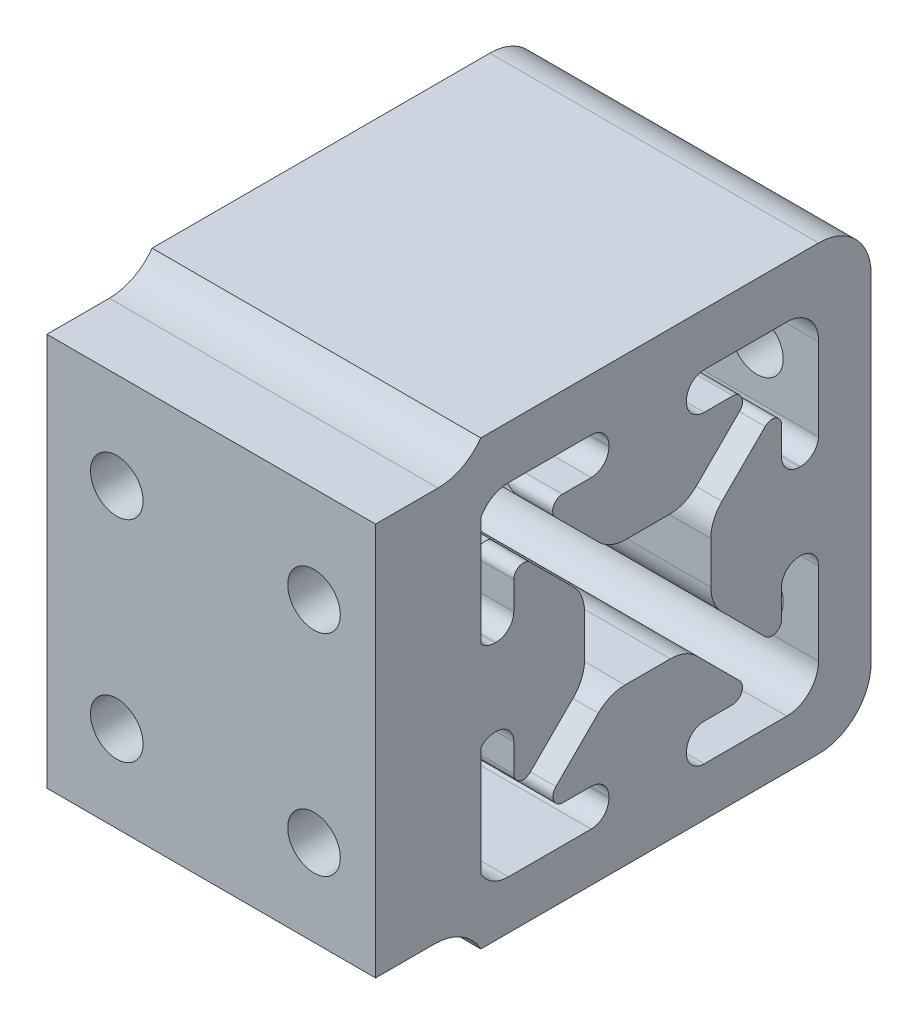
SolidWorks part; units mm, degrees
ref_plane "Front Plane" through (0, 0, 0) normal (0, 0, 1) x (1, 0, 0)
ref_plane "Top Plane" through (0, 0, 0) normal (0, 1, 0) x (1, 0, 0)
ref_plane "Right Plane" through (0, 0, 0) normal (1, 0, 0) x (0, 0, -1)
sketch "Sketch1" plane through (0, 0, 0) normal (0, 0, 1) x (1, 0, 0)
  line L1 (-7.5, -8) -> (7.5, -8) construction
  line L2 (-7.5, -8) -> (-7.5, 8) construction
  line L3 (-7.5, 8) -> (7.5, 8) construction
  line L4 (7.5, -8) -> (7.5, 8) construction
  line L5 (-7.5, -8) -> (7.5, 8) construction
  line L6 (-7.5, 8) -> (7.5, -8) construction
  line L7 (-12.8154, -14.5728) -> (12.1846, -14.5728)
  line L8 (-12.8154, -14.5728) -> (-12.8154, 15.3272)
  line L9 (-12.8154, 15.3272) -> (12.1846, 15.3272)
  line L10 (12.1846, -14.5728) -> (12.1846, 15.3272)
  line L11 (-12.8154, -14.5728) -> (12.1846, 15.3272) construction
  line L12 (-12.8154, 15.3272) -> (12.1846, -14.5728) construction
  circle A0 centre (-7.5, 8) radius 2
  circle A1 centre (7.5, 8) radius 2
  circle A2 centre (7.5, -8) radius 2
  circle A3 centre (-7.5, -8) radius 2
  point P0 (0, 0)
  point P6 (0, 0)
  dimension "D3" = 4
  dimension "D1" = 16
  dimension "D2" = 15
  dimension "D6" = 29.9
  dimension "D7" = 25
  dimension "D8" = 5.3154
  dimension "D4" = 2
  dimension "D5" = 2
extrude "Boss-Extrude1" add sketch "Sketch1" along normal blind 5
sketch "Sketch2" plane through (0, 0, 0) normal (1, 0, 0) x (0, 0, -1)
  line L44 (5.5011, -8.6063) -> (8.7285, -5.3848) construction
  line L54 (10.9715, -4.4569) -> (14.4154, -4.4569) construction
  line L55 (16.6584, -5.3848) -> (19.8857, -8.6063) construction
  line L56 (19.1225, -10.4513) -> (16.9936, -10.4513) construction
  line L57 (15.9455, -11.4994) -> (15.9455, -11.6142) construction
  line L58 (16.9936, -12.6623) -> (18.0212, -12.6623) construction
  line L59 (19.0404, -12.6623) -> (22.2582, -12.6623) construction
  line L60 (25.3869, -9.5337) -> (25.3869, -6.3158) construction
  line L61 (25.3869, -5.2967) -> (25.3869, -4.2691) construction
  line L62 (24.3388, -3.221) -> (24.224, -3.221) construction
  line L63 (23.1759, -4.2691) -> (23.1759, -6.3889) construction
  line L64 (21.4203, -7.1169) -> (18.1293, -3.8315) construction
  line L65 (17.1975, -1.5845) -> (17.1975, 1.6232) construction
  line L119 (18.1293, 3.8701) -> (21.4203, 7.1556) construction
  line L120 (23.1759, 6.4275) -> (23.1759, 4.3077) construction
  line L121 (24.224, 3.2596) -> (24.3388, 3.2596) construction
  line L122 (25.3869, 4.3077) -> (25.3869, 5.3354) construction
  line L123 (25.3869, 6.3545) -> (25.3869, 9.5723) construction
  line L124 (22.2582, 12.701) -> (19.0404, 12.701) construction
  line L125 (18.0212, 12.701) -> (16.9936, 12.701) construction
  line L126 (15.9455, 11.6529) -> (15.9455, 11.5381) construction
  line L127 (16.9936, 10.49) -> (19.1829, 10.49) construction
  line L128 (19.9146, 8.7214) -> (16.6089, 5.4212) construction
  line L129 (14.3657, 4.4932) -> (11.0212, 4.4932) construction
  line L130 (8.778, 5.4212) -> (5.4723, 8.7214) construction
  line L131 (6.204, 10.49) -> (8.3933, 10.49) construction
  line L132 (9.4414, 11.5381) -> (9.4414, 11.6529) construction
  line L133 (8.3933, 12.701) -> (7.3656, 12.701) construction
  line L134 (6.3465, 12.701) -> (3.1287, 12.701) construction
  line L137 (1.0481, 3.2596) -> (1.1629, 3.2596) construction
  line L138 (2.211, 4.3077) -> (2.211, 6.4275) construction
  line L139 (3.9666, 7.1556) -> (7.2576, 3.8701) construction
  line L140 (8.1894, 1.6232) -> (8.1894, -1.5845) construction
  line L141 (7.2576, -3.8315) -> (3.9666, -7.1169) construction
  line L142 (2.211, -6.3889) -> (2.211, -4.2691) construction
  line L143 (1.1629, -3.221) -> (1.0481, -3.221) construction
  line L146 (3.1287, -12.6623) -> (6.3465, -12.6623) construction
  line L147 (7.3656, -12.6623) -> (8.3933, -12.6623) construction
  line L148 (9.4414, -11.6142) -> (9.4414, -11.4994) construction
  line L149 (8.3933, -10.4513) -> (6.2644, -10.4513) construction
  line L152 (2.1095, -12.6623) -> (3.1287, -12.6623) construction
  line L153 (6.3465, -12.6623) -> (7.3656, -12.6623) construction
  line L154 (18.0212, -12.6623) -> (19.0404, -12.6623) construction
  line L155 (22.2582, -12.6623) -> (23.2773, -12.6623) construction
  line L156 (25.3869, -10.5528) -> (25.3869, -9.5337) construction
  line L157 (25.3869, -6.3158) -> (25.3869, -5.2967) construction
  line L158 (25.3869, 5.3354) -> (25.3869, 6.3545) construction
  line L159 (25.3869, 9.5723) -> (25.3869, 10.5915) construction
  line L160 (23.2773, 12.701) -> (22.2582, 12.701) construction
  line L161 (19.0404, 12.701) -> (18.0212, 12.701) construction
  line L162 (7.3656, 12.701) -> (6.3465, 12.701) construction
  line L163 (3.1287, 12.701) -> (2.1095, 12.701) construction
  line L166 (0, -14.5728) -> (0, 15.3272) construction
  line L167 (0, -14.5728) -> (0, -11.7171)
  line L172 (1.0481, 2.9596) -> (1.1629, 2.9596)
  line L173 (2.511, 4.3077) -> (2.511, 6.4275)
  line L174 (3.7546, 6.9433) -> (7.0456, 3.6578)
  line L175 (7.8894, 1.6232) -> (7.8894, -1.5845)
  line L176 (7.0456, -3.6191) -> (3.7546, -6.9046)
  line L177 (2.511, -6.3889) -> (2.511, -4.2691)
  line L178 (1.1629, -2.921) -> (1.0481, -2.921)
  line L183 (2.1095, -12.9623) -> (3.1287, -12.9623)
  line L184 (3.1287, -12.9623) -> (6.3465, -12.9623)
  line L185 (6.3465, -12.9623) -> (7.3656, -12.9623)
  line L186 (7.3656, -12.9623) -> (8.3933, -12.9623)
  line L187 (9.7414, -11.6142) -> (9.7414, -11.4994)
  line L188 (8.3933, -10.1513) -> (6.2644, -10.1513)
  line L189 (5.7131, -8.8186) -> (8.9405, -5.5972)
  line L190 (10.9715, -4.7569) -> (14.4154, -4.7569)
  line L191 (16.4464, -5.5972) -> (19.6738, -8.8186)
  line L192 (19.1225, -10.1513) -> (16.9936, -10.1513)
  line L193 (15.6455, -11.4994) -> (15.6455, -11.6142)
  line L194 (16.9936, -12.9623) -> (18.0212, -12.9623)
  line L195 (18.0212, -12.9623) -> (19.0404, -12.9623)
  line L196 (19.0404, -12.9623) -> (22.2582, -12.9623)
  line L197 (22.2582, -12.9623) -> (23.2773, -12.9623)
  line L198 (25.6869, -10.5528) -> (25.6869, -9.5337)
  line L199 (25.6869, -9.5337) -> (25.6869, -6.3158)
  line L200 (25.6869, -6.3158) -> (25.6869, -5.2967)
  line L201 (25.6869, -5.2967) -> (25.6869, -4.2691)
  line L202 (24.3388, -2.921) -> (24.224, -2.921)
  line L203 (22.8759, -4.2691) -> (22.8759, -6.3889)
  line L204 (21.6322, -6.9046) -> (18.3413, -3.6191)
  line L205 (17.4975, -1.5845) -> (17.4975, 1.6232)
  line L206 (18.3413, 3.6578) -> (21.6322, 6.9433)
  line L207 (22.8759, 6.4275) -> (22.8759, 4.3077)
  line L208 (24.224, 2.9596) -> (24.3388, 2.9596)
  line L209 (25.6869, 4.22) -> (25.6869, 5.2476)
  line L210 (25.6869, 5.2476) -> (25.6869, 6.2667)
  line L211 (25.6869, 6.2667) -> (25.6869, 9.4846)
  line L212 (25.6869, 9.4846) -> (25.6869, 10.5037)
  line L213 (23.2773, 13.001) -> (22.2582, 13.001)
  line L214 (22.2582, 13.001) -> (19.0404, 13.001)
  line L215 (19.0404, 13.001) -> (18.0212, 13.001)
  line L216 (18.0212, 13.001) -> (16.9936, 13.001)
  line L217 (15.6455, 11.6529) -> (15.6455, 11.5381)
  line L218 (16.9936, 10.19) -> (19.1829, 10.19)
  line L219 (19.7026, 8.9337) -> (16.3969, 5.6335)
  line L220 (14.3657, 4.7932) -> (11.0212, 4.7932)
  line L221 (8.99, 5.6335) -> (5.6842, 8.9337)
  line L222 (6.204, 10.19) -> (8.3933, 10.19)
  line L223 (9.7414, 11.5381) -> (9.7414, 11.6529)
  line L224 (8.3933, 13.001) -> (7.3656, 13.001)
  line L225 (7.3656, 13.001) -> (6.3465, 13.001)
  line L226 (6.3465, 13.001) -> (3.1287, 13.001)
  line L227 (3.1287, 13.001) -> (2.1095, 13.001)
  line L229 (29.6869, 16.2395) -> (29.6869, -13.6605)
  line L231 (0, 11.7558) -> (0, 15.3272)
  line L232 (0, -3.4212) -> (0, 3.4599)
  line L233 (0, 15.3272) -> (0, 17.001)
  line L234 (0, 17.001) -> (29.6869, 17.001)
  line L235 (29.6869, 17.001) -> (29.6869, 16.2395)
  line L236 (0, -14.5728) -> (0, -16.6623)
  line L237 (0, -16.6623) -> (29.6869, -16.6623)
  line L238 (29.6869, -16.6623) -> (29.6869, -13.6605)
  arc A90 (5.5011, -8.6063) -> (6.2644, -10.4513) centre (6.2644, -9.371) ccw construction
  arc A91 (10.9715, -4.4569) -> (8.7285, -5.3848) centre (10.9715, -7.6319) ccw construction
  arc A92 (16.6584, -5.3848) -> (14.4154, -4.4569) centre (14.4154, -7.6319) ccw construction
  arc A93 (19.1225, -10.4513) -> (19.8857, -8.6063) centre (19.1225, -9.371) ccw construction
  arc A94 (16.9936, -10.4513) -> (15.9455, -11.4994) centre (16.9936, -11.4994) ccw construction
  arc A95 (15.9455, -11.6142) -> (16.9936, -12.6623) centre (16.9936, -11.6142) ccw construction
  arc A98 (23.2773, -12.6623) -> (25.3869, -10.5528) centre (23.2773, -10.5528) ccw construction
  arc A101 (25.3869, -4.2691) -> (24.3388, -3.221) centre (24.3388, -4.2691) ccw construction
  arc A102 (24.224, -3.221) -> (23.1759, -4.2691) centre (24.224, -4.2691) ccw construction
  arc A103 (21.4203, -7.1169) -> (23.1759, -6.3889) centre (22.1471, -6.3889) ccw construction
  arc A104 (17.1975, -1.5845) -> (18.1293, -3.8315) centre (20.3725, -1.5845) ccw construction
  arc A105 (18.1293, 3.8701) -> (17.1975, 1.6232) centre (20.3725, 1.6232) ccw construction
  arc A106 (23.1759, 6.4275) -> (21.4203, 7.1556) centre (22.1471, 6.4275) ccw construction
  arc A107 (23.1759, 4.3077) -> (24.224, 3.2596) centre (24.224, 4.3077) ccw construction
  arc A108 (24.3388, 3.2596) -> (25.3869, 4.3077) centre (24.3388, 4.3077) ccw construction
  arc A111 (25.3869, 10.5915) -> (23.2773, 12.701) centre (23.2773, 10.5915) ccw construction
  arc A114 (16.9936, 12.701) -> (15.9455, 11.6529) centre (16.9936, 11.6529) ccw construction
  arc A115 (15.9455, 11.5381) -> (16.9936, 10.49) centre (16.9936, 11.5381) ccw construction
  arc A116 (19.9146, 8.7214) -> (19.1829, 10.49) centre (19.1829, 9.4543) ccw construction
  arc A117 (14.3657, 4.4932) -> (16.6089, 5.4212) centre (14.3657, 7.6681) ccw construction
  arc A118 (8.778, 5.4212) -> (11.0212, 4.4932) centre (11.0212, 7.6681) ccw construction
  arc A119 (6.204, 10.49) -> (5.4723, 8.7214) centre (6.204, 9.4543) ccw construction
  arc A120 (8.3933, 10.49) -> (9.4414, 11.5381) centre (8.3933, 11.5381) ccw construction
  arc A121 (9.4414, 11.6529) -> (8.3933, 12.701) centre (8.3933, 11.6529) ccw construction
  arc A128 (1.1629, 3.2596) -> (2.211, 4.3077) centre (1.1629, 4.3077) ccw construction
  arc A129 (3.9666, 7.1556) -> (2.211, 6.4275) centre (3.2398, 6.4275) ccw construction
  arc A130 (8.1894, 1.6232) -> (7.2576, 3.8701) centre (5.0144, 1.6232) ccw construction
  arc A131 (7.2576, -3.8315) -> (8.1894, -1.5845) centre (5.0144, -1.5845) ccw construction
  arc A132 (2.211, -6.3889) -> (3.9666, -7.1169) centre (3.2398, -6.3889) ccw construction
  arc A133 (2.211, -4.2691) -> (1.1629, -3.221) centre (1.1629, -4.2691) ccw construction
  arc A140 (8.3933, -12.6623) -> (9.4414, -11.6142) centre (8.3933, -11.6142) ccw construction
  arc A141 (9.4414, -11.4994) -> (8.3933, -10.4513) centre (8.3933, -11.4994) ccw construction
  arc A142 (2.1095, 13.001) -> (0, 11.7558) centre (2.1095, 10.5915) ccw
  arc A143 (0, 3.4599) -> (1.0481, 2.9596) centre (1.0481, 4.3077) ccw
  arc A144 (1.1629, 2.9596) -> (2.511, 4.3077) centre (1.1629, 4.3077) ccw
  arc A145 (3.7546, 6.9433) -> (2.511, 6.4275) centre (3.2398, 6.4275) ccw
  arc A146 (7.8894, 1.6232) -> (7.0456, 3.6578) centre (5.0144, 1.6232) ccw
  arc A147 (7.0456, -3.6191) -> (7.8894, -1.5845) centre (5.0144, -1.5845) ccw
  arc A148 (2.511, -6.3889) -> (3.7546, -6.9046) centre (3.2398, -6.3889) ccw
  arc A149 (2.511, -4.2691) -> (1.1629, -2.921) centre (1.1629, -4.2691) ccw
  arc A150 (1.0481, -2.921) -> (0, -3.4212) centre (1.0481, -4.2691) ccw
  arc A151 (0, -11.7171) -> (2.1095, -12.9623) centre (2.1095, -10.5528) ccw
  arc A152 (8.3933, -12.9623) -> (9.7414, -11.6142) centre (8.3933, -11.6142) ccw
  arc A153 (9.7414, -11.4994) -> (8.3933, -10.1513) centre (8.3933, -11.4994) ccw
  arc A154 (5.7131, -8.8186) -> (6.2644, -10.1513) centre (6.2644, -9.371) ccw
  arc A155 (10.9715, -4.7569) -> (8.9405, -5.5972) centre (10.9715, -7.6319) ccw
  arc A156 (16.4464, -5.5972) -> (14.4154, -4.7569) centre (14.4154, -7.6319) ccw
  arc A157 (19.1225, -10.1513) -> (19.6738, -8.8186) centre (19.1225, -9.371) ccw
  arc A158 (16.9936, -10.1513) -> (15.6455, -11.4994) centre (16.9936, -11.4994) ccw
  arc A159 (15.6455, -11.6142) -> (16.9936, -12.9623) centre (16.9936, -11.6142) ccw
  arc A160 (23.2773, -12.9623) -> (25.6869, -10.5528) centre (23.2773, -10.5528) ccw
  arc A161 (25.6869, -4.2691) -> (24.3388, -2.921) centre (24.3388, -4.2691) ccw
  arc A162 (24.224, -2.921) -> (22.8759, -4.2691) centre (24.224, -4.2691) ccw
  arc A163 (21.6322, -6.9046) -> (22.8759, -6.3889) centre (22.1471, -6.3889) ccw
  arc A164 (17.4975, -1.5845) -> (18.3413, -3.6191) centre (20.3725, -1.5845) ccw
  arc A165 (18.3413, 3.6578) -> (17.4975, 1.6232) centre (20.3725, 1.6232) ccw
  arc A166 (22.8759, 6.4275) -> (21.6322, 6.9433) centre (22.1471, 6.4275) ccw
  arc A167 (22.8759, 4.3077) -> (24.224, 2.9596) centre (24.224, 4.3077) ccw
  arc A168 (24.3388, 2.9596) -> (25.6869, 4.22) centre (24.3416, 4.3077) ccw
  arc A169 (25.6869, 10.5037) -> (23.2773, 13.001) centre (23.2789, 10.5915) ccw
  arc A170 (16.9936, 13.001) -> (15.6455, 11.6529) centre (16.9936, 11.6529) ccw
  arc A171 (15.6455, 11.5381) -> (16.9936, 10.19) centre (16.9936, 11.5381) ccw
  arc A172 (19.7026, 8.9337) -> (19.1829, 10.19) centre (19.1829, 9.4543) ccw
  arc A173 (14.3657, 4.7932) -> (16.3969, 5.6335) centre (14.3657, 7.6681) ccw
  arc A174 (8.99, 5.6335) -> (11.0212, 4.7932) centre (11.0212, 7.6681) ccw
  arc A175 (6.204, 10.19) -> (5.6842, 8.9337) centre (6.204, 9.4543) ccw
  arc A176 (8.3933, 10.19) -> (9.7414, 11.5381) centre (8.3933, 11.5381) ccw
  arc A177 (9.7414, 11.6529) -> (8.3933, 13.001) centre (8.3933, 11.6529) ccw
  dimension "D5" = 1.0481
  dimension "D1" = 0
  dimension "D10" = 0.1111
  dimension "D11" = 0.4579
  dimension "D12" = 0.0288
  dimension "D13" = 0.0604
  dimension "D14" = 0.0821
  dimension "D15" = 0.5391
  dimension "D16" = 0.6634
  dimension "D18" = 0.8237
  dimension "D19" = 10.49
  dimension "D9" = 4
  dimension "D17" = 29.6869
  dimension "D20" = 4
other "AlignGroup1"
other "AlignGroup2" parameters "D5"=5.207, "D2"=5.207, "D3"=1.0804, "D4"=3.175, "D6"=2.1095, "D7"=1.0288, "D8"=1.0357, "D1"=0.1686, "D9"=108.2533, "D10"=82.8664, "D11"=0.1015, "D12"=0.9177, "D13"=0.1111, "D14"=0.7268, "D15"=1.0478, "D16"=0.4579, "D17"=0.0288, "D18"=0.7029, "D19"=0.0604, "D20"=0.0821, "D21"=0.911, "D22"=0.1081, "D23"=0.8237, "D24"=0.5391, "D25"=0.0495, "D26"=0.6634, "D27"=1.5301, "D28"=0.0497, "D29"=1.654, "D30"=1.6905, "D31"=0.0497, "D32"=1.5301, "D33"=0.6634, "D34"=0.0495, "D35"=0.5391, "D36"=0.8237, "D37"=0.1081, "D38"=0.911, "D39"=0.0821, "D40"=0.0604, "D41"=0.7029, "D42"=0.0288, "D43"=0.4579, "D44"=1.0478, "D45"=0.7268, "D46"=0.1111, "D47"=0.9177, "D48"=0.1015, "D49"=21.883, "D50"=22.8007, "D51"=22.9022, "D52"=22.9022, "D53"=25.0117
extrude "Boss-Extrude2" add sketch "Sketch2" along normal up to surface and the other way up to surface up to face at (12.1846, 0.3772, 2.5) other way up to face at (-12.8154, 0.3772, 2.5)
fillet "Fillet1" radius 4 4 edges at (-0.3154, 17.001, -29.6869) (-0.3154, -16.6623, -29.6869) (-0.3154, 15.3272, 0) (-0.3154, -14.5728, 0)
sketch "Sketch5" plane through (0, 0, 5) normal (0, 0, 1) x (1, 0, 0)
  circle A0 centre (-7.5, -8) radius 2 construction
  circle A1 centre (7.5, -8) radius 2 construction
  circle A2 centre (7.5, 8) radius 2 construction
  circle A3 centre (-7.5, 8) radius 2 construction
  circle A8 centre (-7.5, -8) radius 2
  circle A9 centre (7.5, -8) radius 2
  circle A10 centre (7.5, 8) radius 2
  circle A11 centre (-7.5, 8) radius 2
extrude "Cut-Extrude1" cut sketch "Sketch5" against normal through all
sketch "Sketch6" plane through (0, 0, 5) normal (0, 0, 1) x (1, 0, 0)
  line L4 (12.1846, -14.5728) -> (12.1846, 15.3272)
  line L5 (12.1846, 15.3272) -> (-12.8154, 15.3272)
  line L6 (-12.8154, 15.3272) -> (-12.8154, -14.5728)
  line L8 (12.1846, -14.5728) -> (12.1846, 15.3272)
  line L10 (-12.8154, 15.3272) -> (-12.8154, -14.5728)
  line L12 (12.1846, 15.3272) -> (-12.8154, 15.3272)
  line L13 (-12.8154, -14.5728) -> (12.1846, -14.5728)
  line L14 (-12.8154, -14.5728) -> (12.1846, -14.5728)
  circle A0 centre (-7.5, -8) radius 2 construction
  circle A1 centre (7.5, -8) radius 2 construction
  circle A2 centre (7.5, 8) radius 2 construction
  circle A3 centre (-7.5, 8) radius 2 construction
  circle A4 centre (-7.5, -8) radius 2 construction
  circle A5 centre (7.5, -8) radius 2 construction
  circle A6 centre (7.5, 8) radius 2 construction
  circle A7 centre (-7.5, 8) radius 2 construction
  circle A8 centre (-7.5, 8) radius 2
  circle A9 centre (7.5, 8) radius 2
  circle A10 centre (7.5, -8) radius 2
  circle A11 centre (-7.5, -8) radius 2
  dimension "D1" = 4
  dimension "D4" = 16
  dimension "D5" = 15
  dimension "D7" = 5.3154
  dimension "D6" = 0
  dimension "D2" = 2
  dimension "D3" = 2
extrude "Boss-Extrude3" add sketch "Sketch6" along normal blind 3
